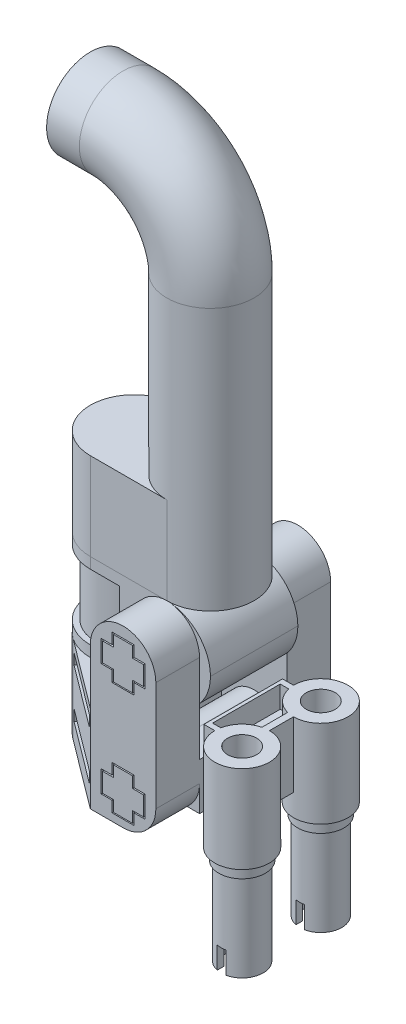
SolidWorks part; units mm, degrees
ref_plane "Front Plane" through (0, 0, 0) normal (0, 0, 1) x (1, 0, 0)
ref_plane "Top Plane" through (0, 0, 0) normal (0, 1, 0) x (1, 0, 0)
ref_plane "Right Plane" through (0, 0, 0) normal (1, 0, 0) x (0, 0, -1)
sketch "Sketch1" plane through (0, 0, 0) normal (0, 1, 0) x (1, 0, 0)
  line L0 (0, 0) -> (-7, 0) construction
  line L1 (0, -4) -> (-7, -4)
  line L2 (0, 4) -> (-7, 4)
  arc A0 (0, -4) -> (0, 4) centre (0, 0) ccw
  arc A1 (-7, 4) -> (-7, -4) centre (-7, 0) ccw
  point P3 (-3.5, 0)
  point P8 (-11, 0)
  point P9 (4, 0)
  dimension "D1" = 15
  dimension "D2" = 4
extrude "Boss-Extrude1" add sketch "Sketch1" along normal blind 8
sketch "Sketch2" plane through (0, 0, 0) normal (0, 0, 1) x (1, 0, 0)
  line L0 (-11, 32) -> (-8, 32)
  line L1 (0, 24) -> (0, 8)
  line L2 (-7, 8) -> (-11, 8) construction
  arc A0 (-8, 32) -> (0, 24) centre (-8, 24) cw
  dimension "D1" = 8
  dimension "D2" = 24
sweep "Sweep1" add path "Sketch2" circular profile diameter 8 parameters "D3"=8
sketch "Sketch16" plane through (-11, 0, 0) normal (-1, 0, 0) x (0, 0, 1)
  circle A0 centre (0, 32.0666) radius 2
  dimension "D1" = 4
sketch "Sketch17" plane through (0, 0, 0) normal (0, 0, 1) x (1, 0, 0)
  line L0 (0, 8) -> (0, 24)
  line L1 (-4, 24) -> (4, 24) construction
  line L3 (-11, 34.0666) -> (-11, 30.0666) construction
  line L4 (-11, 32.0666) -> (-8, 32.0666)
  line L5 (0, 24.0666) -> (0, 24)
  arc A0 (-8, 32.0666) -> (0, 24.0666) centre (-8, 24.0666) cw
  dimension "D1" = 8
sweep "Cut-Sweep1" cut profiles "Sketch16" path "Sketch17"
sketch "Sketch18" plane through (0, 0, 0) normal (0, -1, 0) x (1, 0, 0)
  line L0 (-7, 4) -> (4, 4)
  line L1 (4, 4) -> (4, -4)
  line L2 (4, -4) -> (-7, -4)
  arc A0 (-7, 4) -> (-7, -4) centre (-7, 0) ccw
extrude "Boss-Extrude2" add sketch "Sketch18" along normal blind 8 separate body
fillet "Fillet1" radius 4 1 edges at (4, -8, 0)
fillet "Fillet2" radius 4 1 edges at (4, 0, 0)
sketch "Sketch19" plane through (0, -8, 0) normal (0, -1, 0) x (1, 0, 0)
  line L0 (-2.2158, 0.3807) -> (0, 0.3807)
  line L1 (0, -4) -> (0, 4) construction
  line L2 (0, 0.3807) -> (0, -0.6611)
  line L3 (0, -0.6611) -> (-2.2465, -0.6611)
  arc A0 (-2.2158, 0.3807) -> (-2.2465, -0.6611) centre (-7, 0) ccw
  circle A1 centre (-7, 0) radius 3.5
extrude "Cut-Extrude1" cut sketch "Sketch19" against normal blind 6 from offset 1 offset against normal yes
sketch "Sketch20" plane through (0, -8, 0) normal (0, -1, 0) x (1, 0, 0)
  line L0 (-11, 0) -> (-3, 0) construction
  line L1 (-9.4, 3.2) -> (-3, 8)
  line L2 (-3, 4) -> (-3, -4)
  line L3 (-3, 0) -> (-9.4, 0)
  line L4 (-9.4, -3.2) -> (-9.4, 3.2)
  line L5 (-9.4, -3.2) -> (-3, -8)
  line L6 (-3, 8) -> (-3, -8)
  arc A0 (-7, 4) -> (-7, -4) centre (-7, 0) ccw construction
  dimension "D1" = 16
  dimension "D2" = 8
  dimension "D7" = 6.4
extrude "Boss-Extrude3" add sketch "Sketch20" along normal blind 8 separate body
sketch "Sketch22" plane through (0, 0, -4) normal (0, 0, -1) x (-1, 0, 0)
  line L0 (0, -3) -> (0, -13) construction
  line L1 (3, -3) -> (3, -13)
  line L2 (-3, -3) -> (-3, -13)
  arc A0 (3, -3) -> (-3, -3) centre (0, -3) ccw
  arc A1 (-3, -13) -> (3, -13) centre (0, -13) ccw
  point P2 (0, -8)
  point P7 (0, 0)
  point P8 (0, -16)
  dimension "D1" = 16
  dimension "D2" = 6
extrude "Boss-Extrude4" add sketch "Sketch22" along normal blind 4 separate body
sketch "Sketch23" plane through (0, 0, 4) normal (0, 0, 1) x (1, 0, 0)
  line L0 (0, -3) -> (0, -13) construction
  line L1 (3, -3) -> (3, -13)
  line L2 (-3, -3) -> (-3, -13)
  arc A0 (3, -3) -> (-3, -3) centre (0, -3) ccw
  arc A1 (-3, -13) -> (3, -13) centre (0, -13) ccw
  point P2 (0, -8)
  dimension "D2" = 6
extrude "Boss-Extrude11" add sketch "Sketch23" along normal blind 4 separate body
sketch "Sketch25" plane through (0, 0, 8) normal (0, 0, 1) x (1, 0, 0)
  line L0 (0, -16) -> (-3, -16)
  line L1 (-3, -13) -> (-3, -16)
  line L2 (-3, -16) -> (-3, -8) construction
  arc A0 (-3, -13) -> (3, -13) centre (0, -13) ccw construction
  arc A1 (-3, -13) -> (0, -16) centre (0, -13) ccw
extrude "Boss-Extrude12" add sketch "Sketch25" against normal blind 4
sketch "Sketch26" plane through (0, 0, -8) normal (0, 0, -1) x (-1, 0, 0)
  line L0 (3, -13) -> (3, -16)
  line L1 (3, -16) -> (0, -16)
  arc A0 (0, -16) -> (3, -13) centre (0, -13) ccw
  arc A1 (-3, -13) -> (3, -13) centre (0, -13) ccw construction
extrude "Boss-Extrude13" add sketch "Sketch26" against normal blind 4
sketch "Sketch27" plane through (0, 0, -8) normal (0, 0, -1) x (-1, 0, 0)
  line L1 (-1, -1.5) -> (1, -1.5)
  line L2 (-1, -1.5) -> (-1, -2.5)
  line L3 (-1, -5.5) -> (1, -5.5)
  line L4 (1, -1.5) -> (1, -2.5)
  line L6 (-0.875, -2.6341) -> (-1.875, -2.6341)
  line L7 (2, -2.5) -> (1, -2.5)
  line L8 (2, -2.5) -> (2, -4.5)
  line L9 (2, -4.5) -> (1, -4.5)
  line L10 (-2, -2.5) -> (-2, -4.5)
  line L11 (1.875, -4.3841) -> (0.875, -4.3841)
  line L16 (1.875, -4.3841) -> (1.875, -2.6341)
  line L17 (1.875, -2.6341) -> (0.875, -2.6341)
  line L21 (-1.875, -4.3841) -> (-1.875, -2.6341)
  line L24 (-1, -2.5) -> (-2, -2.5)
  line L26 (-1, -4.5) -> (-1, -5.5)
  line L28 (1, -4.5) -> (1, -5.5)
  line L29 (-1, -4.5) -> (-2, -4.5)
  line L30 (0.875, -5.3932) -> (-0.875, -5.3932)
  line L31 (0.875, -5.3932) -> (0.875, -4.3841)
  line L32 (0.875, -1.625) -> (-0.875, -1.625)
  line L34 (-0.875, -5.3932) -> (-0.875, -4.3841)
  line L38 (-0.875, -2.6341) -> (-0.875, -1.625)
  line L41 (-0.875, -4.3841) -> (-1.875, -4.3841)
  line L42 (0.875, -2.6341) -> (0.875, -1.625)
  line L43 (-1, -11.3645) -> (1, -11.3645)
  line L44 (-1, -11.3645) -> (-1, -12.3645)
  line L45 (-1, -15.3645) -> (1, -15.3645)
  line L46 (1, -11.3645) -> (1, -12.3645)
  line L47 (-0.875, -12.4986) -> (-1.875, -12.4986)
  line L48 (2, -12.3645) -> (1, -12.3645)
  line L49 (2, -12.3645) -> (2, -14.3645)
  line L50 (2, -14.3645) -> (1, -14.3645)
  line L51 (-2, -12.3645) -> (-2, -14.3645)
  line L52 (1.875, -14.2486) -> (0.875, -14.2486)
  line L53 (1.875, -14.2486) -> (1.875, -12.4986)
  line L54 (1.875, -12.4986) -> (0.875, -12.4986)
  line L55 (-1.875, -14.2486) -> (-1.875, -12.4986)
  line L56 (-1, -12.3645) -> (-2, -12.3645)
  line L57 (-1, -14.3645) -> (-1, -15.3645)
  line L58 (1, -14.3645) -> (1, -15.3645)
  line L59 (-1, -14.3645) -> (-2, -14.3645)
  line L60 (0.875, -15.2577) -> (-0.875, -15.2577)
  line L61 (0.875, -15.2577) -> (0.875, -14.2486)
  line L62 (0.875, -11.4895) -> (-0.875, -11.4895)
  line L63 (-0.875, -15.2577) -> (-0.875, -14.2486)
  line L64 (-0.875, -12.4986) -> (-0.875, -11.4895)
  line L65 (-0.875, -14.2486) -> (-1.875, -14.2486)
  line L66 (0.875, -12.4986) -> (0.875, -11.4895)
  point P0 (0, -3.5091)
  point P5 (0, -3.5091)
  point P12 (0, -13.3736)
  point P17 (0, -13.3736)
  point P25 (0, -1.5)
  point P29 (0, -3.5091)
  point P31 (0, -11.3645)
  point P36 (0, -3.5091)
  point P45 (0, -13.3736)
  point P51 (0, -13.3736)
  point P60 (0, -11.4895)
  point P61 (-1.875, -13.3736)
  point P62 (0, -1.625)
  point P64 (-1.875, -3.5091)
  dimension "D1" = 2
  dimension "D2" = 4
  dimension "D3" = 2
  dimension "D4" = 4
  dimension "D5" = 2
  dimension "D6" = 4
  dimension "D7" = 2
  dimension "D8" = 4
  dimension "D9" = 1.75
  dimension "D10" = 3.75
  dimension "D11" = 1.75
  dimension "D12" = 1.75
  dimension "D13" = 3.75
  dimension "D14" = 1.75
extrude "Cut-Extrude3" cut sketch "Sketch27" against normal blind 2
sketch "Sketch30" plane through (0, 0, 8) normal (0, 0, 1) x (1, 0, 0)
  line L0 (-1, -0.9886) -> (1, -0.9886)
  line L1 (-1, -0.9886) -> (-1, -1.9886)
  line L2 (-1, -4.9886) -> (1, -4.9886)
  line L3 (1, -0.9886) -> (1, -1.9886)
  line L4 (-0.875, -2.1227) -> (-1.875, -2.1227)
  line L5 (1.9975, -1.9886) -> (1, -1.9886)
  line L6 (1.9975, -1.9886) -> (1.9975, -3.9886)
  line L7 (1.9975, -3.9886) -> (1, -3.9886)
  line L8 (-2.0025, -1.9886) -> (-2.0025, -3.9886)
  line L9 (1.875, -3.8727) -> (0.875, -3.8727)
  line L10 (1.875, -3.8727) -> (1.875, -2.1227)
  line L11 (1.875, -2.1227) -> (0.875, -2.1227)
  line L12 (-1.875, -3.8727) -> (-1.875, -2.1227)
  line L13 (-1, -1.9886) -> (-2.0025, -1.9886)
  line L14 (-1, -3.9886) -> (-1, -4.9886)
  line L15 (1, -3.9886) -> (1, -4.9886)
  line L16 (-1, -3.9886) -> (-2.0025, -3.9886)
  line L17 (0.875, -4.8818) -> (-0.875, -4.8818)
  line L18 (0.875, -4.8818) -> (0.875, -3.8727)
  line L19 (0.875, -1.1136) -> (-0.875, -1.1136)
  line L20 (-0.875, -4.8818) -> (-0.875, -3.8727)
  line L21 (-0.875, -2.1227) -> (-0.875, -1.1136)
  line L22 (-0.875, -3.8727) -> (-1.875, -3.8727)
  line L23 (0.875, -2.1227) -> (0.875, -1.1136)
  line L24 (-1, -11.3203) -> (1, -11.3203)
  line L25 (-1, -11.3203) -> (-1, -12.3203)
  line L26 (-1, -15.3203) -> (1, -15.3203)
  line L27 (1, -11.3203) -> (1, -12.3203)
  line L28 (-0.875, -12.4544) -> (-1.875, -12.4544)
  line L29 (2, -12.3203) -> (1, -12.3203)
  line L30 (2, -12.3203) -> (2, -14.3203)
  line L31 (2, -14.3203) -> (1, -14.3203)
  line L32 (-2, -12.3203) -> (-2, -14.3203)
  line L33 (1.875, -14.2044) -> (0.875, -14.2044)
  line L34 (1.875, -14.2044) -> (1.875, -12.4544)
  line L35 (1.875, -12.4544) -> (0.875, -12.4544)
  line L36 (-1.875, -14.2044) -> (-1.875, -12.4544)
  line L37 (-1, -12.3203) -> (-2, -12.3203)
  line L38 (-1, -14.3203) -> (-1, -15.3203)
  line L39 (1, -14.3203) -> (1, -15.3203)
  line L40 (-1, -14.3203) -> (-2, -14.3203)
  line L41 (0.875, -15.2135) -> (-0.875, -15.2135)
  line L42 (0.875, -15.2135) -> (0.875, -14.2044)
  line L43 (0.875, -11.4453) -> (-0.875, -11.4453)
  line L44 (-0.875, -15.2135) -> (-0.875, -14.2044)
  line L45 (-0.875, -12.4544) -> (-0.875, -11.4453)
  line L46 (-0.875, -14.2044) -> (-1.875, -14.2044)
  line L47 (0.875, -12.4544) -> (0.875, -11.4453)
  point P0 (0, -2.9977)
  point P5 (-0.0025, -2.9977)
  point P12 (0, -0.9886)
  point P15 (0, -2.9977)
  point P20 (0, -2.9977)
  point P29 (0, -1.1136)
  point P30 (-1.875, -2.9977)
  point P34 (0, -13.3294)
  point P39 (0, -13.3294)
  point P46 (0, -11.3203)
  point P49 (0, -13.3294)
  point P54 (0, -13.3294)
  point P63 (0, -11.4453)
  point P64 (-1.875, -13.3294)
  dimension "D1" = 2
  dimension "D2" = 4
  dimension "D3" = 2
  dimension "D4" = 4
  dimension "D5" = 1.75
  dimension "D6" = 3.75
  dimension "D7" = 1.75
  dimension "D8" = 2
  dimension "D9" = 4
  dimension "D10" = 2
  dimension "D11" = 4
  dimension "D12" = 1.75
  dimension "D13" = 3.75
  dimension "D14" = 1.75
extrude "Cut-Extrude6" cut sketch "Sketch30" against normal blind 2
sketch "Sketch33" plane through (0, 0, 4) normal (0, 0, -1) x (-1, 0, 0)
  circle A0 centre (0, -13.5331) radius 2.4669
extrude "Boss-Extrude14" add sketch "Sketch33" along normal up to body separate body
sketch "Sketch34" plane through (0, -8, 0) normal (0, -1, 0) x (1, 0, 0)
  line L0 (-9.4, -3.2) -> (-9.4, 3.2) construction
  line L1 (-9.4, 3.2) -> (-9.4, -3.2)
  arc A0 (-9.4, 3.2) -> (-9.4, -3.2) centre (-7, 0) ccw
  arc A1 (-7, 4) -> (-7, -4) centre (-7, 0) ccw construction
extrude "Boss-Extrude16" add sketch "Sketch34" along normal blind 8 separate body
sketch "Sketch35" plane through (3, 0, 0) normal (1, 0, 0) x (0, 0, -1)
  line L0 (-4, -13) -> (-4, -3) construction
  line L1 (-4, -11.0948) -> (4, -11.0948)
  line L2 (-4, -11.0948) -> (-4, -15.3826)
  line L3 (-4, -15.3826) -> (4, -15.3826)
  line L4 (4, -11.0948) -> (4, -15.3826)
  line L5 (4, -16) -> (4, -11.0662) construction
extrude "Boss-Extrude17" add sketch "Sketch35" against normal up to body separate body
ref_plane "Plane1" through (0, -8.5, 0) normal (0, 1, 0) x (1, 0, 0)
sketch "Sketch36" plane through (0, -8.5, 0) normal (0, 1, 0) x (1, 0, 0)
  line L0 (3, 0) -> (0.8069, 0) construction
  line L1 (3, 3.6) -> (4, 3.6)
  line L2 (3, 3.6) -> (3, -3.6)
  line L3 (3, -3.6) -> (4, -3.6)
  line L4 (4, 3.6) -> (4, -3.6)
  line L5 (3, 4) -> (3, -4) construction
  point P9 (3, 0)
  dimension "D1" = 7.2
  dimension "D2" = 1
extrude "Boss-Extrude18" add sketch "Sketch36" against normal blind 6
sketch "Sketch37" plane through (0, -8.5, 0) normal (0, 1, 0) x (1, 0, 0)
  circle A0 centre (6.4999, 3.6) radius 2.4999
  circle A1 centre (6.4999, -3.6) radius 2.4999
  dimension "D1" = 2
  dimension "D2" = 4.9998
extrude "Boss-Extrude19" add sketch "Sketch37" against normal blind 8 separate body
sketch "Sketch38" plane through (0, -8.5, 0) normal (0, 1, 0) x (1, 0, 0)
  line L0 (4, -3.6) -> (4, 3.6) construction
  line L1 (4, 3.6) -> (4, -3.6)
  line L2 (6.4999, 1.1001) -> (6.4999, -1.1001)
  arc A0 (4, 3.6) -> (6.4999, 1.1001) centre (6.4999, 3.6) ccw
  circle A1 centre (6.4999, 3.6) radius 2.4999 construction
  arc A2 (4, -3.6) -> (6.4999, -1.1001) centre (6.4999, -3.6) cw
  circle A3 centre (6.4999, -3.6) radius 2.4999 construction
extrude "Boss-Extrude20" add sketch "Sketch38" against normal blind 6
sketch "Sketch39" plane through (0, -8.5, 0) normal (0, 1, 0) x (1, 0, 0)
  line L0 (3.2985, 3.0896) -> (4.0884, 3.0896)
  line L1 (3.2985, 3.0896) -> (3.2985, -3.1041)
  line L2 (3.2985, -3.1041) -> (4.0497, -3.1041)
  line L3 (5.8895, 1.1757) -> (5.8895, -1.1758)
  line L4 (3, 3.6) -> (3, -3.6) construction
  arc A2 (4.0884, 3.0896) -> (5.8895, 1.1757) centre (6.5377, 3.5901) ccw
  arc A3 (5.8895, -1.1758) -> (4.0497, -3.1041) centre (6.4999, -3.6) ccw
  dimension "D1" = 2.4999
  dimension "D2" = 0.2985
  dimension "D3" = 1.0497
  dimension "D4" = 1.0884
  dimension "D5" = 2.8895
  dimension "D6" = 3.5377
  dimension "D7" = 4.7757
extrude "Cut-Extrude7" cut sketch "Sketch39" against normal blind 2
sketch "Sketch40" plane through (0, -16.5, 0) normal (0, -1, 0) x (1, 0, 0)
  circle A1 centre (6.4999, 3.6) radius 2.123
  circle A2 centre (6.4999, -3.6) radius 2.123
  circle A3 centre (6.4999, 3.6) radius 2.4999 construction
  dimension "D2" = 4.246
  dimension "D3" = 7.2
  dimension "D1" = 2
extrude "Boss-Extrude21" add sketch "Sketch40" along normal blind 1 separate body
sketch "Sketch41" plane through (0, -17.5, 0) normal (0, -1, 0) x (1, 0, 0)
  circle A0 centre (6.4999, 3.6) radius 1.923
  circle A1 centre (6.4999, 3.6) radius 1.323
  circle A2 centre (6.4999, -3.6) radius 1.923
  circle A3 centre (6.4999, -3.6) radius 1.323
  circle A4 centre (6.4999, 3.6) radius 2.123 construction
  dimension "D3" = 2.646
  dimension "D4" = 7.2
  dimension "D1" = 0.6
  dimension "D2" = 2
extrude "Boss-Extrude22" add sketch "Sketch41" along normal blind 8 separate body
sketch "Sketch42" plane through (0, -25.5, 0) normal (0, -1, 0) x (1, 0, 0)
  circle A0 centre (6.4999, 3.6) radius 1.323
  circle A1 centre (6.4999, -3.6) radius 1.325
  dimension "D1" = 2.646
  dimension "D2" = 2.65
extrude "Cut-Extrude9" cut sketch "Sketch42" against normal blind 18 contours A0 | A1
sketch "Sketch44" plane through (0, -25.5, 0) normal (0, -1, 0) x (1, 0, 0)
  line L0 (6.0999, 5.6008) -> (6.0999, 1.6008)
  line L3 (6.8999, 5.5992) -> (6.8999, 1.6008)
  line L4 (6.0999, -1.5992) -> (6.0999, -5.5992)
  line L5 (6.8999, -1.6008) -> (6.8999, -5.5992)
  line L6 (6.8999, 5.5992) -> (6.0999, 1.6008) construction
  line L7 (6.0999, 5.6008) -> (6.8999, 1.6008) construction
  arc A2 (6.0999, 1.6008) -> (6.8999, 1.6008) centre (6.4999, 3.4962) ccw
  arc A3 (6.0999, 5.6008) -> (6.8999, 5.5992) centre (6.4962, 3.7045) cw
  circle A4 centre (6.4999, 3.6) radius 1.923 construction
  arc A5 (6.0999, -5.5992) -> (6.8999, -5.5992) centre (6.4999, -3.7038) ccw
  arc A6 (6.0999, -1.5992) -> (6.8999, -1.6008) centre (6.4962, -3.4955) cw
  point P6 (6.4999, 3.6)
  point P7 (6.4999, 1.559)
  point P19 (6.4999, 4.923)
  point P21 (5.1769, 3.6)
  dimension "D2" = 0.8
  dimension "D4" = 1.9372
  dimension "D1" = 2
  dimension "D3" = 4
  dimension "D5" = 7.2
  dimension "D6" = 0.0037
extrude "Cut-Extrude12" cut sketch "Sketch44" against normal blind 2
sketch "Sketch47" plane through (-4.92, 0, -6.56) normal (-0.6, 0, -0.8) x (-0.8, 0, 0.6)
  line L0 (-2.4, -16) -> (-2.4, -8) construction
  line L1 (-1.9429, -8.8072) -> (5.0319, -8.8072)
  line L2 (-1.9429, -8.8072) -> (-1.9429, -9.8072)
  line L3 (-1.9429, -9.8072) -> (5.0319, -9.8072)
  line L4 (5.0319, -8.8072) -> (5.0319, -9.8072)
  line L5 (-1.9429, -13.273) -> (5.0319, -13.273)
  line L6 (-1.9429, -13.273) -> (-1.9429, -14.273)
  line L7 (-1.9429, -14.273) -> (5.0319, -14.273)
  line L8 (5.0319, -13.273) -> (5.0319, -14.273)
  line L9 (5.6, -8) -> (-2.4, -8) construction
  dimension "D1" = 1
  dimension "D2" = 0.4571
  dimension "D3" = 7.4319
  dimension "D4" = 0.8072
  dimension "D5" = 5.273
extrude "Cut-Extrude15" cut sketch "Sketch47" against normal blind 1
mirror "Mirror2" about plane through (0, 0, 0) normal (0, 0, 1) of "Cut-Extrude15"
